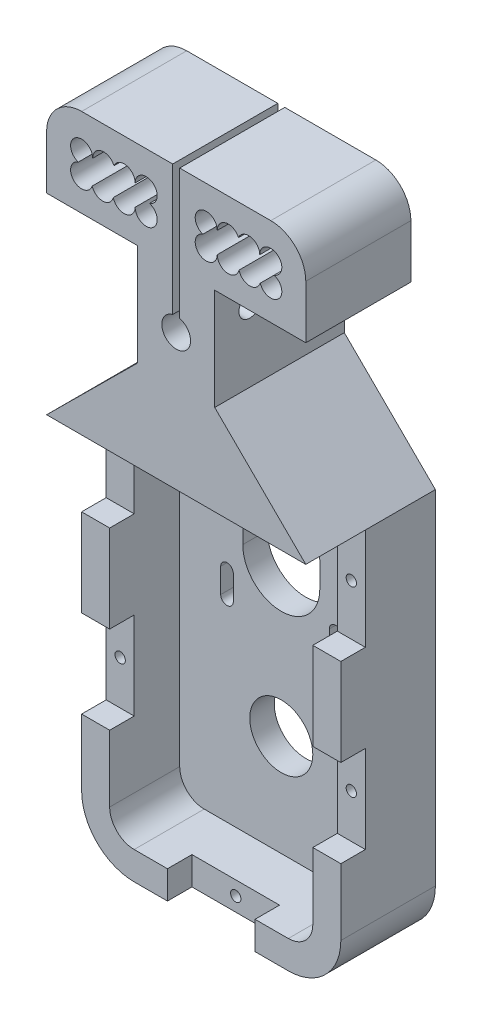
SolidWorks part; units mm, degrees
note: The reader was unsure of these and kept them because the rebuilt part matched: shared geometry of "Croquis2<7>", "Croquis2<12>", "Croquis2<14>".
ref_plane "Alzado" through (0, 0, 0) normal (0, 0, 1) x (1, 0, 0)
ref_plane "Planta" through (0, 0, 0) normal (0, 1, 0) x (1, 0, 0)
ref_plane "Vista lateral" through (0, 0, 0) normal (1, 0, 0) x (0, 0, -1)
sketch "Croquis2" plane through (0, 0, 0) normal (0, 0, 1) x (1, 0, 0)
  line L0 (-30.7866, 48.816) -> (-5.7866, 48.816)
  line L1 (-5.7866, 48.816) -> (-5.7866, 40.816)
  line L2 (-5.7866, 40.816) -> (-30.7866, 40.816)
  line L3 (-30.7866, 48.816) -> (-30.7866, 40.816)
  line L5 (-22.5241, 25.0911) -> (-22.5241, 24.7943)
  line L7 (-18.1703, 25.0911) -> (-18.1703, 24.7943)
  line L8 (-5.7866, 48.816) -> (18.7134, 48.816)
  line L9 (-55.2866, 48.816) -> (-30.7866, 48.816)
  line L10 (18.7134, 48.816) -> (18.7134, 19.816)
  line L11 (-55.2866, 48.816) -> (-55.2866, 19.816)
  line L12 (-55.2866, 19.816) -> (-47.2866, 19.816)
  line L13 (-47.2866, 19.816) -> (-47.2866, 40.816)
  line L14 (-47.2866, 40.816) -> (-30.7866, 40.816)
  line L15 (18.7134, 19.816) -> (10.7134, 19.816)
  line L16 (10.7134, 19.816) -> (10.7134, 40.816)
  line L17 (10.7134, 40.816) -> (-5.7866, 40.816)
  line L18 (-55.2866, 19.816) -> (-55.2866, -5.184)
  line L19 (-55.2866, -5.184) -> (-47.2866, -5.184)
  line L20 (-47.2866, -5.184) -> (-47.2866, 19.816)
  line L21 (10.7134, 19.816) -> (10.7134, -5.184)
  line L22 (18.7134, 19.816) -> (18.7134, -5.184)
  line L23 (10.7134, -5.184) -> (18.7134, -5.184)
  line L24 (-55.2866, -5.184) -> (-55.2866, -30.184)
  line L25 (18.7134, -5.184) -> (18.7134, -30.184)
  line L26 (-47.2866, -5.184) -> (-47.2866, -30.184)
  line L27 (-31.9866, 6.2053) -> (-31.9866, -0.7947)
  line L28 (10.7134, -5.184) -> (10.7134, -30.184)
  line L29 (-55.2866, -30.184) -> (-47.2866, -30.184)
  line L30 (18.7134, -30.184) -> (10.7134, -30.184)
  line L31 (-55.2866, -30.184) -> (-55.2866, -49.184)
  line L32 (18.7134, -30.184) -> (18.7134, -49.184)
  line L34 (-47.2866, -30.184) -> (-47.2866, -49.184)
  line L35 (10.7134, -30.184) -> (10.7134, -49.184)
  line L36 (-47.2866, -49.184) -> (-55.2866, -49.184)
  line L37 (10.7134, -49.184) -> (18.7134, -49.184)
  line L38 (-40.2866, -56.184) -> (-30.7866, -56.184)
  line L39 (3.7134, -56.184) -> (3.7134, -64.184)
  line L40 (-30.7866, -56.184) -> (-30.7866, -64.184)
  line L41 (-19.2866, 103.616) -> (-29.2866, 103.616)
  line L42 (-30.7866, -64.184) -> (-40.2866, -64.184)
  line L43 (-30.7866, -56.184) -> (-5.7866, -56.184)
  line L44 (-40.2866, -64.184) -> (-40.2866, -56.184)
  line L45 (-5.7866, -56.184) -> (-5.7866, -64.184)
  line L46 (-5.7866, -64.184) -> (-30.7866, -64.184)
  line L47 (3.7134, -64.184) -> (-5.7866, -64.184)
  line L48 (-5.7866, -56.184) -> (3.7134, -56.184)
  line L49 (-4.5866, 30.2053) -> (-4.5866, 37.2053)
  line L50 (-7.2866, 21.7053) -> (-7.2866, 14.7053)
  line L51 (-0.9866, 30.2053) -> (-0.9866, 37.2053)
  line L52 (-29.2866, 21.7053) -> (-29.2866, 14.7053)
  line L53 (-0.9866, 6.2053) -> (-0.9866, -0.7947)
  line L54 (-4.5866, 6.2053) -> (-4.5866, -0.7947)
  line L55 (-35.5866, 6.2053) -> (-35.5866, -0.7947)
  line L56 (-35.5866, 30.2053) -> (-35.5866, 37.2053)
  line L57 (-31.9866, 30.2053) -> (-31.9866, 37.2053)
  line L58 (-17.2866, 103.616) -> (-7.2866, 103.616)
  line L59 (-55.2866, 48.816) -> (-29.2866, 74.616)
  line L63 (-29.2866, 103.616) -> (-29.2866, 74.616)
  line L64 (-19.2866, 103.616) -> (-19.2866, 91.616)
  line L65 (18.7134, 48.816) -> (-7.2866, 74.616)
  line L66 (-17.2866, 103.616) -> (-17.2866, 91.616)
  line L67 (-7.2866, 103.616) -> (-7.2866, 74.616)
  arc A0 (-55.2866, -49.184) -> (-40.2866, -64.184) centre (-40.2866, -49.184) ccw
  arc A1 (18.7134, -49.184) -> (3.7134, -64.184) centre (3.7134, -49.184) cw
  arc A2 (-47.2866, -49.184) -> (-40.2866, -56.184) centre (-40.2866, -49.184) ccw
  arc A3 (3.7134, -56.184) -> (10.7134, -49.184) centre (3.7134, -49.184) ccw
  circle A4 centre (-18.2866, -27.184) radius 9
  arc A5 (-7.2866, 21.7053) -> (-29.2866, 21.7053) centre (-18.2866, 21.7053) ccw
  arc A7 (-29.2866, 14.7053) -> (-7.2866, 14.7053) centre (-18.2866, 14.7053) ccw
  arc A8 (-0.9866, 37.2053) -> (-4.5866, 37.2053) centre (-2.7866, 37.2053) ccw
  arc A9 (-4.5866, 30.2053) -> (-0.9866, 30.2053) centre (-2.7866, 30.2053) ccw
  arc A10 (-4.5866, 6.2053) -> (-0.9866, 6.2053) centre (-2.7866, 6.2053) cw
  arc A11 (-0.9866, -0.7947) -> (-4.5866, -0.7947) centre (-2.7866, -0.7947) cw
  arc A12 (-35.5866, -0.7947) -> (-31.9866, -0.7947) centre (-33.7866, -0.7947) ccw
  arc A13 (-31.9866, 6.2053) -> (-35.5866, 6.2053) centre (-33.7866, 6.2053) ccw
  arc A14 (-31.9866, 30.2053) -> (-35.5866, 30.2053) centre (-33.7866, 30.2053) cw
  arc A15 (-35.5866, 37.2053) -> (-31.9866, 37.2053) centre (-33.7866, 37.2053) cw
  arc A16 (-19.2866, 91.616) -> (-17.2866, 91.616) centre (-18.2866, 87.6398) ccw
extrude "Saliente-Extruir1" add sketch "Croquis2" along normal blind 7 contours L48 A3 L35 L28 L21 L16 L17 L2 L14 L13 L20 L26 L34 A2 L38 L43 A13 L27 A12 L55 A9 L49 A8 L51 A7 L52 A5 L50 A4 L53 A11 L54 A10 L56 A15 L57 A14
extrude "Saliente-Extruir3" add sketch "Croquis2<7>" along normal blind 27 contours L0 L3 L2 L1 | L19 L20 L12 L18 | L36 L34 L29 L31 | A2 L36 A0 L44 | L44 L42 L40 L38 | L48 L45 L47 L39 | A3 L39 A1 L37 | L35 L37 L32 L30 | L21 L23 L22 L15
sketch "Croquis2<7>" plane through (0, 0, 0) normal (0, 0, 1) x (1, 0, 0) same geometry as "Croquis2"
sketch "Croquis3" plane through (0, 0, 0) normal (0, 0, -1) x (-1, 0, 0)
  circle A0 centre (18.2866, -27.184) radius 11.1
extrude "Saliente-Extruir4" add sketch "Croquis2<12>" along normal blind 20 contours L17 L16 L15 L10 L8 L1 | L13 L14 L3 L9 L11 L12 | L24 L29 L26 L19 | L30 L25 L23 L28 | L46 L45 L43 L40
sketch "Croquis2<12>" plane through (0, 0, 0) normal (0, 0, 1) x (1, 0, 0) same geometry as "Croquis2"
extrude "Saliente-Extruir5" add sketch "Croquis2<14>" along normal blind 37 contours A16 L64 L41 L63 L59 L9 L0 L8 L65 L67 L58 L66
sketch "Croquis2<14>" plane through (0, 0, 0) normal (0, 0, 1) x (1, 0, 0) same geometry as "Croquis2"
sketch "Croquis4" plane through (0, 0, 27) normal (0, 0, 1) x (1, 0, 0)
  circle A0 centre (-51.2866, 34.316) radius 1.475
  circle A1 centre (-51.2866, -17.684) radius 1.475
  circle A2 centre (-18.2866, -60.184) radius 1.475
  circle A3 centre (14.7134, -17.684) radius 1.475
  circle A4 centre (14.7134, 34.316) radius 1.475
extrude "Cortar-Extruir2" cut sketch "Croquis4" against normal blind 14
sketch "Croquis10" plane through (-7.2866, 0, 0) normal (1, 0, 0) x (0, 0, -1)
  circle A0 centre (-9, 94.816) radius 1.9
  circle A1 centre (-18, 94.816) radius 1.9
  circle A2 centre (-27, 94.816) radius 1.9
extrude "Cortar-Extruir3" cut sketch "Croquis10" against normal blind 22
sketch "Croquis11" plane through (-7.2866, 0, 0) normal (1, 0, 0) x (0, 0, -1)
  circle A0 centre (-27, 94.816) radius 3.1
  circle A1 centre (-18, 94.816) radius 3.1
  circle A2 centre (-9, 94.816) radius 3.1
extrude "Cortar-Extruir4" cut sketch "Croquis11" against normal blind 6
sketch "Croquis12" plane through (-29.2866, 0, 0) normal (-1, 0, 0) x (0, 0, 1)
  line L7 (21.2332, 94.816) -> (19.6166, 97.616)
  line L8 (19.6166, 97.616) -> (16.3834, 97.616)
  line L9 (16.3834, 97.616) -> (14.7668, 94.816)
  line L10 (14.7668, 94.816) -> (16.3834, 92.016)
  line L11 (16.3834, 92.016) -> (19.6166, 92.016)
  line L12 (19.6166, 92.016) -> (21.2332, 94.816)
  line L13 (12.2332, 94.816) -> (10.6166, 97.616)
  line L14 (10.6166, 97.616) -> (7.3834, 97.616)
  line L15 (7.3834, 97.616) -> (5.7668, 94.816)
  line L16 (5.7668, 94.816) -> (7.3834, 92.016)
  line L17 (7.3834, 92.016) -> (10.6166, 92.016)
  line L18 (10.6166, 92.016) -> (12.2332, 94.816)
  line L25 (30.2332, 94.816) -> (28.6166, 97.616)
  line L26 (28.6166, 97.616) -> (25.3834, 97.616)
  line L27 (25.3834, 97.616) -> (23.7668, 94.816)
  line L28 (23.7668, 94.816) -> (25.3834, 92.016)
  line L29 (25.3834, 92.016) -> (28.6166, 92.016)
  line L30 (28.6166, 92.016) -> (30.2332, 94.816)
  circle A0 centre (9, 94.816) radius 2.8 construction
  circle A1 centre (18, 94.816) radius 2.8 construction
  circle A2 centre (27, 94.816) radius 2.8 construction
extrude "Cortar-Extruir5" cut sketch "Croquis12" against normal blind 6
sketch "Croquis13" plane through (0, 0, 37) normal (0, 0, -1) x (-1, 0, 0)
  line L0 (7.2866, 103.616) -> (-18.7134, 103.616)
  line L1 (-18.7134, 48.816) -> (55.2866, 48.816)
  line L3 (-8.7134, 128.816) -> (17.2866, 128.816)
  line L5 (18.2866, 87.6398) -> (18.2866, 132.9809)
  line L6 (-18.7134, 103.616) -> (-18.7134, 118.816)
  line L7 (19.2866, 103.616) -> (19.2866, 128.816)
  line L8 (17.2866, 103.616) -> (17.2866, 128.816)
  line L9 (29.2866, 103.616) -> (55.2866, 103.616)
  line L10 (55.2866, 103.616) -> (55.2866, 118.816)
  line L11 (45.2866, 128.816) -> (19.2866, 128.816)
  arc A1 (-8.7134, 128.816) -> (-18.7134, 118.816) centre (-8.7134, 118.816) ccw
  circle A2 centre (-8.7134, 118.816) radius 3.15
  circle A3 centre (-2.4134, 118.816) radius 3.15
  circle A4 centre (3.412, 118.7711) radius 3.15
  circle A5 centre (9.712, 118.7711) radius 3.15
  circle A17 centre (-8.7134, 112.816) radius 3.15
  circle A26 centre (-2.7134, 112.816) radius 3.15
  circle A27 centre (3.412, 112.7711) radius 3.15
  circle A30 centre (9.712, 112.7711) radius 3.15
  arc A42 (45.2866, 128.816) -> (55.2866, 118.816) centre (45.2866, 118.816) cw
  circle A43 centre (26.8613, 112.7711) radius 3.15
  circle A44 centre (33.1613, 112.7711) radius 3.15
  circle A45 centre (39.2866, 112.816) radius 3.15
  circle A46 centre (45.2866, 112.816) radius 3.15
  circle A47 centre (26.8613, 118.7711) radius 3.15
  circle A48 centre (33.1613, 118.7711) radius 3.15
  circle A49 centre (38.9866, 118.816) radius 3.15
  circle A50 centre (45.2866, 118.816) radius 3.15
extrude "Saliente-Extruir10" add sketch "Croquis13" along normal blind 27
sketch "Croquis15" plane through (0, 0, 10) normal (0, 0, -1) x (-1, 0, 0)
  line L0 (17.2866, 103.616) -> (-18.7134, 103.616)
  line L1 (-18.7134, 103.616) -> (-18.7134, 118.816)
  line L2 (-8.7134, 128.816) -> (17.2866, 128.816)
  line L3 (17.2866, 128.816) -> (17.2866, 103.616)
  line L4 (18.2866, 87.6398) -> (18.2866, 134.8048)
  line L5 (55.2866, 103.616) -> (55.2866, 118.816)
  line L6 (19.2866, 103.616) -> (55.2866, 103.616)
  line L7 (19.2866, 128.816) -> (19.2866, 103.616)
  line L8 (45.2866, 128.816) -> (19.2866, 128.816)
  arc A0 (-18.7134, 118.816) -> (-8.7134, 128.816) centre (-8.7134, 118.816) cw
  arc A1 (55.2866, 118.816) -> (45.2866, 128.816) centre (45.2866, 118.816) ccw
extrude "Saliente-Extruir12" add sketch "Croquis15" along normal blind 3 contours L5 A1 L8 L7 L6
